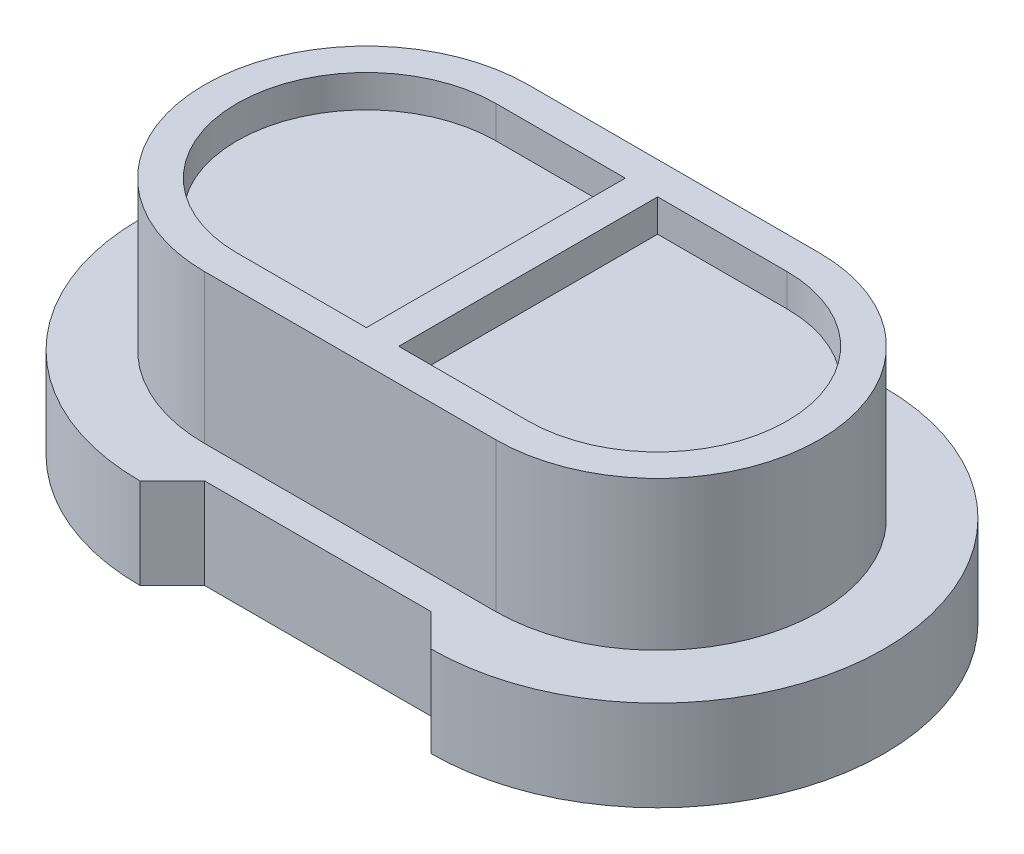
SolidWorks part; units mm, degrees
material "ABS"
ref_plane "Спереди" through (0, 0, 0) normal (0, 0, 1) x (1, 0, 0)
ref_plane "Сверху" through (0, 0, 0) normal (0, 1, 0) x (1, 0, 0)
ref_plane "Справа" through (0, 0, 0) normal (1, 0, 0) x (0, 0, -1)
sketch "Эскиз1" plane through (0, 0, 0) normal (0, 1, 0) x (1, 0, 0)
  line L0 (2.25, 0) -> (-2.25, 0) construction
  line L5 (2.25, -3.5) -> (-2.25, -3.5)
  line L6 (2.25, 3.5) -> (-2.25, 3.5)
  line L7 (-2.25, 3.5) -> (-1.75, 3)
  line L8 (-1.75, 3) -> (1.75, 3)
  line L9 (1.75, 3) -> (2.25, 3.5)
  line L10 (0, 3.5) -> (0, -3.5) construction
  line L11 (-5.75, 0) -> (5.75, 0) construction
  line L12 (1.75, -3) -> (2.25, -3.5)
  line L13 (-1.75, -3) -> (1.75, -3)
  line L14 (-2.25, -3.5) -> (-1.75, -3)
  line L15 (2.25, 0) -> (-2.25, 0) construction
  line L16 (2.25, -2.5) -> (-2.25, -2.5)
  line L17 (2.25, 2.5) -> (-2.25, 2.5)
  line L20 (2.25, -2) -> (-2.25, -2)
  line L21 (0.25, -2.5) -> (-0.25, -2.5)
  line L22 (0.25, -2.5) -> (0.25, 2.5)
  line L23 (0.25, 2.5) -> (-0.25, 2.5)
  line L24 (-0.25, -2.5) -> (-0.25, 2.5)
  line L25 (0.25, -2.5) -> (-0.25, 2.5) construction
  line L26 (0.25, 2.5) -> (-0.25, -2.5) construction
  line L27 (2.25, 2) -> (-2.25, 2)
  arc A0 (2.25, -3.5) -> (2.25, 3.5) centre (2.25, 0) ccw
  arc A1 (-2.25, 3.5) -> (-2.25, -3.5) centre (-2.25, 0) ccw
  arc A2 (2.25, -2.5) -> (2.25, 2.5) centre (2.25, 0) ccw
  arc A3 (-2.25, 2.5) -> (-2.25, -2.5) centre (-2.25, 0) ccw
  arc A6 (-2.25, 2) -> (-2.25, -2) centre (-2.25, 0) ccw
  arc A7 (2.25, -2) -> (2.25, 2) centre (2.25, 0) ccw
  point P2 (0, 0)
  point P9 (-5.75, 0)
  point P10 (5.75, 0)
  point P24 (0, 0)
  point P29 (-4.75, 0)
  point P30 (4.75, 0)
  point P37 (0, 0)
  dimension "D1" = 11.5
  dimension "D2" = 7
  dimension "D3" = 4.5
  dimension "D4" = 3.5
  dimension "D5" = 0.5
  dimension "D6" = 5
  dimension "D7" = 9.5
  dimension "D9" = 0.5
  dimension "D8" = 0.5
extrude "Бобышка-Вытянуть1" add sketch "Эскиз1" against normal blind 1.4 contours L7 A1 L14 L13 L12 A0 L9 L8 A3 L17 A2 L16 | A6 L27 L24 L17 A3 L16 L20 | L27 L22 L17 L24 | A7 L20 L22 L16 A2 L17 L27 | L24 L16 L22 L20 region at (2.0952, 0, 3.1548) region at (1.25, 0, 2.4327) region at (0, 0, 2.25) region at (-1.25, 0, 2.4327) region at (0, 0, -2.25)
extrude "Бобышка-Вытянуть2" add sketch "Эскиз1<3>" along normal blind 2.3 contours A6 L27 L24 L17 A3 L16 L20 | L27 L22 L17 L24 | L24 L16 L22 L20 | L22 L27 L24 L20 | A7 L20 L22 L16 A2 L17 L27 region at (1.25, 0, 2.4327) region at (0, 0, 2.25) region at (-1.25, 0, 2.4327) region at (0, 0, 0) region at (0, 0, -2.25)
sketch "Эскиз1<3>" plane through (0, 0, 0) normal (0, 1, 0) x (1, 0, 0) same geometry as "Эскиз1"
ref_plane "Плоскость1" through (0, 1.8, 0) normal (0, 1, 0) x (1, 0, 0)
sketch "Эскиз2" plane through (0, 1.8, 0) normal (0, 1, 0) x (1, 0, 0)
  line L0 (2.25, 2) -> (0.25, 2) construction
  line L1 (2.25, -2) -> (0.25, -2) construction
  line L2 (0.25, -2) -> (0.25, 2) construction
  line L3 (-0.25, -2) -> (-2.25, -2) construction
  line L4 (-0.25, -2) -> (-0.25, 2) construction
  line L5 (-0.25, 2) -> (-2.25, 2) construction
  line L6 (2.25, 2) -> (0.25, 2)
  line L7 (2.25, -2) -> (0.25, -2)
  line L8 (0.25, -2) -> (0.25, 2)
  line L9 (-0.25, -2) -> (-2.25, -2)
  line L10 (-0.25, -2) -> (-0.25, 2)
  line L11 (-0.25, 2) -> (-2.25, 2)
  arc A0 (2.25, -2) -> (2.25, 2) centre (2.25, 0) ccw construction
  arc A1 (-2.25, 2) -> (-2.25, -2) centre (-2.25, 0) ccw construction
  arc A2 (2.25, -2) -> (2.25, 2) centre (2.25, 0) ccw
  arc A3 (-2.25, 2) -> (-2.25, -2) centre (-2.25, 0) ccw
extrude "Бобышка-Вытянуть3" add sketch "Эскиз2" against normal blind 0.2 separate body
sketch "Эскиз3" plane through (0, 1.6, 0) normal (0, -1, 0) x (1, 0, 0)
  line L0 (2.25, 2) -> (0.25, 2) construction
  line L1 (0.25, 2) -> (0.25, -2) construction
  line L2 (0.25, -2) -> (2.25, -2) construction
  line L3 (-0.25, -2) -> (-0.25, 2) construction
  line L4 (-0.25, 2) -> (-2.25, 2) construction
  line L5 (-2.25, -2) -> (-0.25, -2) construction
  line L6 (2.25, 2) -> (0.25, 2)
  line L7 (0.25, 2) -> (0.25, -2)
  line L8 (0.25, -2) -> (2.25, -2)
  line L9 (-0.25, -2) -> (-0.25, 2)
  line L10 (-0.25, 2) -> (-2.25, 2)
  line L11 (-2.25, -2) -> (-0.25, -2)
  line L12 (0, 1.5347) -> (0, -1.7849) construction
  line L13 (-0.45, -1) -> (-2.45, -1)
  line L14 (-0.45, -1) -> (-0.45, 1)
  line L15 (-0.45, 1) -> (-2.45, 1)
  line L16 (-2.45, -1) -> (-2.45, 1)
  line L17 (-0.45, -1) -> (-2.45, 1) construction
  line L18 (-0.45, 1) -> (-2.45, -1) construction
  line L19 (0.45, 1) -> (2.45, 1)
  line L20 (2.45, -1) -> (2.45, 1)
  line L21 (0.45, -1) -> (2.45, -1)
  line L22 (0.45, -1) -> (0.45, 1)
  arc A0 (2.25, -2) -> (2.25, 2) centre (2.25, 0) ccw construction
  arc A1 (-2.25, 2) -> (-2.25, -2) centre (-2.25, 0) ccw construction
  arc A2 (2.25, -2) -> (2.25, 2) centre (2.25, 0) ccw
  arc A3 (-2.25, 2) -> (-2.25, -2) centre (-2.25, 0) ccw
  point P3 (-1.45, 0)
  dimension "D1" = 2
  dimension "D2" = 2
  dimension "D3" = 0.2
extrude "Бобышка-Вытянуть4" add sketch "Эскиз3" along normal blind 0.2 separate body
